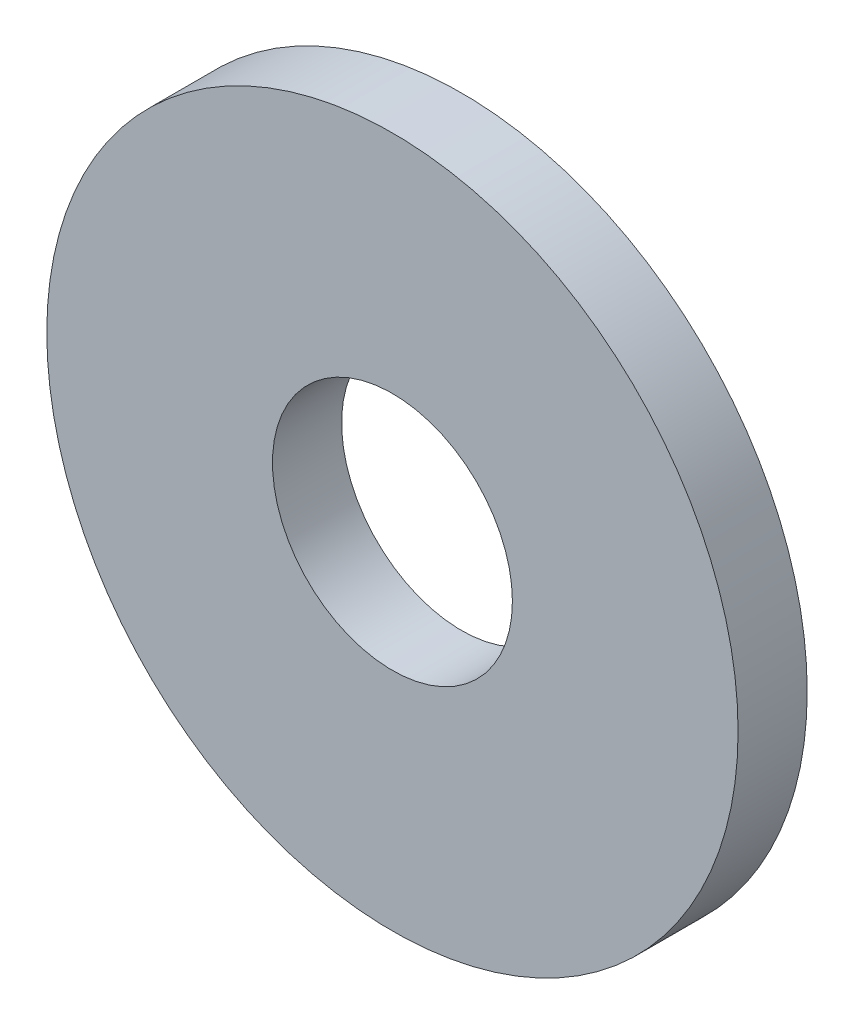
SolidWorks part; units mm, degrees
ref_plane "Front Plane" through (0, 0, 0) normal (0, 0, 1) x (1, 0, 0)
ref_plane "Top Plane" through (0, 0, 0) normal (0, 1, 0) x (1, 0, 0)
ref_plane "Right Plane" through (0, 0, 0) normal (1, 0, 0) x (0, 0, -1)
sketch "Sketch1" plane through (0, 0, 0) normal (0, 0, 1) x (1, 0, 0)
  circle A0 centre (0, 0) radius 8.5
  circle A1 centre (0, 0) radius 2.95
  dimension "D1" = 5.9
  dimension "D2" = 17
extrude "Boss-Extrude1" add sketch "Sketch1" along normal blind 1.7
equation "\"smallPulleyTeeth\"= 15"
equation "\"largePulleyTeeth\"= 40"
equation "\"eighthThick\"= 2.9mm"
equation "\"sixteenthThick\"= 1.7mm"
equation "\"wheelEighthThick\"=3.0mm"
equation "\"quarterThick\"=5.9mm"
equation "\"OD\"= 145mm"
equation "\"puckAngle\"= 60.5deg"
equation "\"puckDiam\"= 76.5mm"
equation "\"axlePress\"= 5.9mm"
equation "\"D1@Sketch1\"=\"axlePress\""
equation "\"D1@Boss-Extrude1\"=\"sixteenthThick\""
